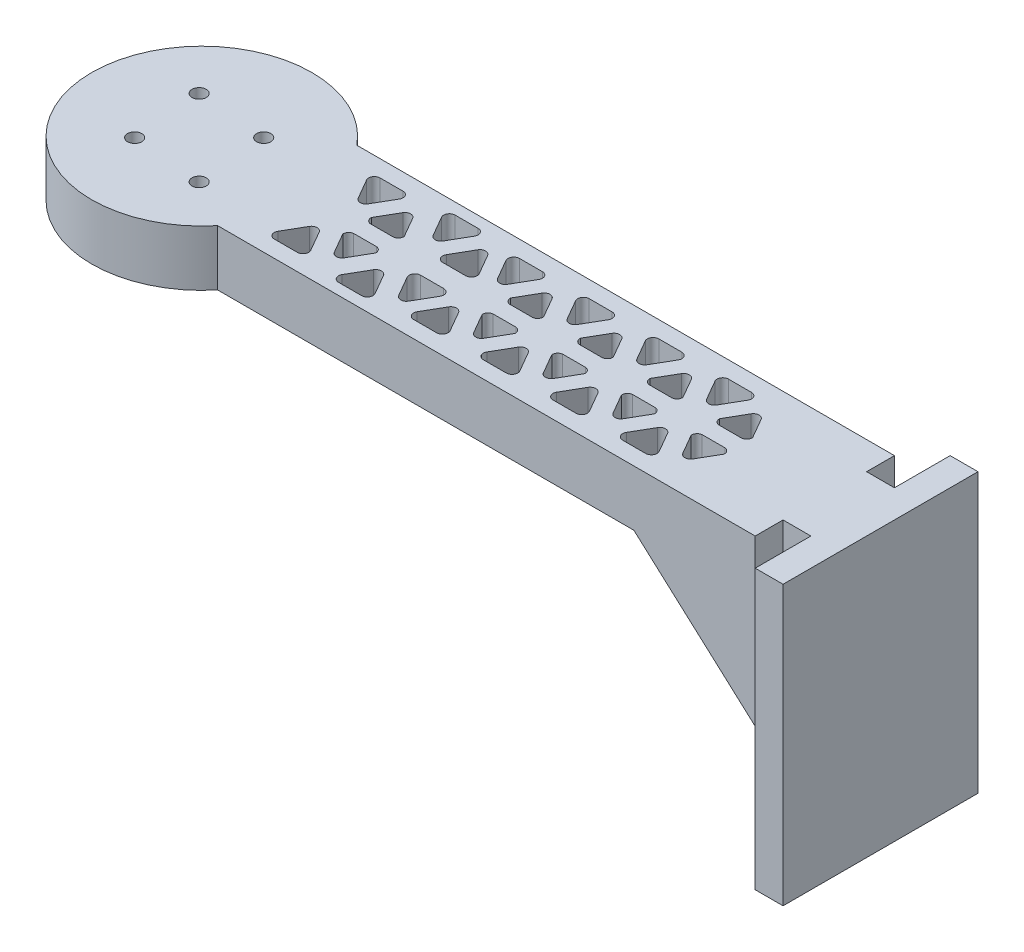
SolidWorks part; units mm, degrees
note: The reader was unsure of these and kept them because the rebuilt part matched: shared geometry of "Sketch2<3>".
ref_plane "Front Plane" through (0, 0, 0) normal (0, 0, 1) x (1, 0, 0)
ref_plane "Top Plane" through (0, 0, 0) normal (0, 1, 0) x (1, 0, 0)
ref_plane "Right Plane" through (0, 0, 0) normal (1, 0, 0) x (0, 0, -1)
sketch "Sketch1" plane through (0, 0, 0) normal (0, 1, 0) x (1, 0, 0)
  line L0 (19.7818, 0.4757) -> (121.8484, 0.4757) construction
  line L1 (15.332, 12.9757) -> (121.8484, 12.9757)
  line L2 (15.332, -12.0243) -> (121.8484, -12.0243)
  line L3 (121.8484, 12.9757) -> (121.8484, -12.0243)
  line L4 (22.5013, 9.9757) -> (26.6358, 9.9757)
  line L5 (27.5225, 8.4396) -> (25.4552, 4.8613)
  line L6 (23.682, 4.8613) -> (21.6147, 8.4396)
  line L7 (29.935, 6.6184) -> (27.8677, 3.0401)
  line L8 (33.7755, 3.0322) -> (31.7082, 6.6184)
  line L9 (28.7543, 1.9757) -> (32.8889, 1.9757)
  line L21 (37.9612, 5.8205) -> (40.0285, 9.3988)
  line L22 (34.1207, 9.3988) -> (36.188, 5.8205)
  line L23 (39.1419, 10.935) -> (35.0073, 10.935)
  line L26 (45.3949, 2.4553) -> (41.2604, 2.4553)
  line L27 (40.3737, 3.9915) -> (42.441, 7.5777)
  line L28 (44.2142, 7.5777) -> (46.2815, 3.9993)
  line L29 (35.0113, 9.9757) -> (39.1458, 9.9757) [skipped]
  line L30 (40.0325, 8.4396) -> (37.9652, 4.8613) [skipped]
  line L31 (36.192, 4.8613) -> (34.1247, 8.4396) [skipped]
  line L32 (42.445, 6.6184) -> (40.3777, 3.0401) [skipped]
  line L33 (46.2855, 3.0322) -> (44.2182, 6.6184) [skipped]
  line L34 (41.2643, 1.9757) -> (45.3989, 1.9757) [skipped]
  line L35 (47.5213, 9.9757) -> (51.6558, 9.9757)
  line L36 (52.5425, 8.4396) -> (50.4752, 4.8613)
  line L37 (48.702, 4.8613) -> (46.6347, 8.4396)
  line L38 (54.955, 6.6184) -> (52.8877, 3.0401)
  line L39 (58.7955, 3.0322) -> (56.7282, 6.6184)
  line L40 (53.7743, 1.9757) -> (57.9089, 1.9757)
  line L41 (60.0313, 9.9757) -> (64.1658, 9.9757)
  line L42 (65.0525, 8.4396) -> (62.9852, 4.8613)
  line L43 (61.212, 4.8613) -> (59.1447, 8.4396)
  line L44 (67.465, 6.6184) -> (65.3977, 3.0401)
  line L45 (71.3055, 3.0322) -> (69.2382, 6.6184)
  line L46 (66.2843, 1.9757) -> (70.4189, 1.9757)
  line L47 (72.5413, 9.9757) -> (76.6758, 9.9757)
  line L48 (77.5625, 8.4396) -> (75.4952, 4.8613)
  line L49 (73.722, 4.8613) -> (71.6547, 8.4396)
  line L50 (79.975, 6.6184) -> (77.9077, 3.0401)
  line L51 (83.8155, 3.0322) -> (81.7482, 6.6184)
  line L52 (78.7943, 1.9757) -> (82.9289, 1.9757)
  line L53 (85.0513, 9.9757) -> (89.1858, 9.9757)
  line L54 (90.0725, 8.4396) -> (88.0052, 4.8613)
  line L55 (86.232, 4.8613) -> (84.1647, 8.4396)
  line L56 (92.485, 6.6184) -> (90.4177, 3.0401)
  line L57 (96.3255, 3.0322) -> (94.2582, 6.6184)
  line L58 (91.3043, 1.9757) -> (95.4389, 1.9757)
  line L59 (91.3043, -1.0243) -> (95.4389, -1.0243)
  line L60 (96.3255, -2.0808) -> (94.2582, -5.667)
  line L61 (92.485, -5.667) -> (90.4177, -2.0887)
  line L62 (86.232, -3.9098) -> (84.1647, -7.4881)
  line L63 (90.0725, -7.4881) -> (88.0052, -3.9098)
  line L64 (85.0513, -9.0243) -> (89.1858, -9.0243)
  line L65 (78.7943, -1.0243) -> (82.9289, -1.0243)
  line L66 (83.8155, -2.0808) -> (81.7482, -5.667)
  line L67 (79.975, -5.667) -> (77.9077, -2.0887)
  line L68 (73.722, -3.9098) -> (71.6547, -7.4881)
  line L69 (77.5625, -7.4881) -> (75.4952, -3.9098)
  line L70 (72.5413, -9.0243) -> (76.6758, -9.0243)
  line L71 (66.2843, -1.0243) -> (70.4189, -1.0243)
  line L72 (71.3055, -2.0808) -> (69.2382, -5.667)
  line L73 (67.465, -5.667) -> (65.3977, -2.0887)
  line L74 (61.212, -3.9098) -> (59.1447, -7.4881)
  line L75 (65.0525, -7.4881) -> (62.9852, -3.9098)
  line L76 (60.0313, -9.0243) -> (64.1658, -9.0243)
  line L77 (53.7743, -1.0243) -> (57.9089, -1.0243)
  line L78 (58.7955, -2.0808) -> (56.7282, -5.667)
  line L79 (54.955, -5.667) -> (52.8877, -2.0887)
  line L80 (48.702, -3.9098) -> (46.6347, -7.4881)
  line L81 (52.5425, -7.4881) -> (50.4752, -3.9098)
  line L82 (47.5213, -9.0243) -> (51.6558, -9.0243)
  line L83 (44.2142, -6.6262) -> (46.2815, -3.0479)
  line L84 (40.3737, -3.0401) -> (42.441, -6.6262)
  line L85 (45.3949, -1.5039) -> (41.2604, -1.5039)
  line L86 (39.1419, -9.9836) -> (35.0073, -9.9836)
  line L87 (34.1207, -8.4474) -> (36.188, -4.8691)
  line L88 (37.9612, -4.8691) -> (40.0285, -8.4474)
  line L89 (28.7543, -1.0243) -> (32.8889, -1.0243)
  line L90 (33.7755, -2.0808) -> (31.7082, -5.667)
  line L91 (29.935, -5.667) -> (27.8677, -2.0887)
  line L92 (23.682, -3.9098) -> (21.6147, -7.4881)
  line L93 (27.5225, -7.4881) -> (25.4552, -3.9098)
  line L94 (22.5013, -9.0243) -> (26.6358, -9.0243)
  circle A0 centre (0, 0.4757) radius 19.7818
  circle A1 centre (-6.8783, 6.8783) radius 1.2799
  circle A2 centre (5.7923, 5.7923) radius 1.2799
  circle A3 centre (-5.7923, -5.7923) radius 1.2799
  circle A4 centre (6.8783, -6.8783) radius 1.2799
  arc A5 (25.4552, 4.8613) -> (23.682, 4.8613) centre (24.5686, 5.3735) cw
  arc A6 (22.5013, 9.9757) -> (21.6147, 8.4396) centre (22.5013, 8.9518) ccw
  arc A7 (26.6358, 9.9757) -> (27.5225, 8.4396) centre (26.6358, 8.9518) cw
  arc A8 (32.8889, 1.9757) -> (33.7755, 3.0322) centre (32.7524, 2.9905) ccw
  arc A9 (31.7082, 6.6184) -> (29.935, 6.6184) centre (30.8216, 6.1062) ccw
  arc A10 (28.7543, 1.9757) -> (27.8677, 3.0401) centre (28.8905, 2.9906) cw
  arc A20 (35.0073, 10.935) -> (34.1207, 9.3988) centre (35.0073, 9.911) ccw
  arc A21 (39.1419, 10.935) -> (40.0285, 9.3988) centre (39.1419, 9.911) cw
  arc A22 (36.188, 5.8205) -> (37.9612, 5.8205) centre (37.0746, 6.3327) ccw
  arc A23 (45.3949, 2.4553) -> (46.2815, 3.9993) centre (45.3995, 3.4793) ccw
  arc A24 (42.441, 7.5777) -> (44.2142, 7.5777) centre (43.3276, 7.0654) cw
  arc A25 (41.2604, 2.4553) -> (40.3737, 3.9915) centre (41.2604, 3.4793) cw
  arc A26 (37.9652, 4.8613) -> (36.192, 4.8613) centre (37.0786, 5.3735) cw [skipped]
  arc A27 (35.0113, 9.9757) -> (34.1247, 8.4396) centre (35.0113, 8.9518) ccw [skipped]
  arc A28 (39.1458, 9.9757) -> (40.0325, 8.4396) centre (39.1458, 8.9518) cw [skipped]
  arc A29 (45.3989, 1.9757) -> (46.2855, 3.0322) centre (45.2624, 2.9905) ccw [skipped]
  arc A30 (44.2182, 6.6184) -> (42.445, 6.6184) centre (43.3316, 6.1062) ccw [skipped]
  arc A31 (41.2643, 1.9757) -> (40.3777, 3.0401) centre (41.4005, 2.9906) cw [skipped]
  arc A32 (50.4752, 4.8613) -> (48.702, 4.8613) centre (49.5886, 5.3735) cw
  arc A33 (47.5213, 9.9757) -> (46.6347, 8.4396) centre (47.5213, 8.9518) ccw
  arc A34 (51.6558, 9.9757) -> (52.5425, 8.4396) centre (51.6558, 8.9518) cw
  arc A35 (57.9089, 1.9757) -> (58.7955, 3.0322) centre (57.7724, 2.9905) ccw
  arc A36 (56.7282, 6.6184) -> (54.955, 6.6184) centre (55.8416, 6.1062) ccw
  arc A37 (53.7743, 1.9757) -> (52.8877, 3.0401) centre (53.9105, 2.9906) cw
  arc A38 (62.9852, 4.8613) -> (61.212, 4.8613) centre (62.0986, 5.3735) cw
  arc A39 (60.0313, 9.9757) -> (59.1447, 8.4396) centre (60.0313, 8.9518) ccw
  arc A40 (64.1658, 9.9757) -> (65.0525, 8.4396) centre (64.1658, 8.9518) cw
  arc A41 (70.4189, 1.9757) -> (71.3055, 3.0322) centre (70.2824, 2.9905) ccw
  arc A42 (69.2382, 6.6184) -> (67.465, 6.6184) centre (68.3516, 6.1062) ccw
  arc A43 (66.2843, 1.9757) -> (65.3977, 3.0401) centre (66.4205, 2.9906) cw
  arc A44 (75.4952, 4.8613) -> (73.722, 4.8613) centre (74.6086, 5.3735) cw
  arc A45 (72.5413, 9.9757) -> (71.6547, 8.4396) centre (72.5413, 8.9518) ccw
  arc A46 (76.6758, 9.9757) -> (77.5625, 8.4396) centre (76.6758, 8.9518) cw
  arc A47 (82.9289, 1.9757) -> (83.8155, 3.0322) centre (82.7924, 2.9905) ccw
  arc A48 (81.7482, 6.6184) -> (79.975, 6.6184) centre (80.8616, 6.1062) ccw
  arc A49 (78.7943, 1.9757) -> (77.9077, 3.0401) centre (78.9305, 2.9906) cw
  arc A50 (88.0052, 4.8613) -> (86.232, 4.8613) centre (87.1186, 5.3735) cw
  arc A51 (85.0513, 9.9757) -> (84.1647, 8.4396) centre (85.0513, 8.9518) ccw
  arc A52 (89.1858, 9.9757) -> (90.0725, 8.4396) centre (89.1858, 8.9518) cw
  arc A53 (95.4389, 1.9757) -> (96.3255, 3.0322) centre (95.3024, 2.9905) ccw
  arc A54 (94.2582, 6.6184) -> (92.485, 6.6184) centre (93.3716, 6.1062) ccw
  arc A55 (91.3043, 1.9757) -> (90.4177, 3.0401) centre (91.4405, 2.9906) cw
  arc A56 (91.3043, -1.0243) -> (90.4177, -2.0887) centre (91.4405, -2.0391) ccw
  arc A57 (94.2582, -5.667) -> (92.485, -5.667) centre (93.3716, -5.1547) cw
  arc A58 (95.4389, -1.0243) -> (96.3255, -2.0808) centre (95.3024, -2.0391) cw
  arc A59 (89.1858, -9.0243) -> (90.0725, -7.4881) centre (89.1858, -8.0004) ccw
  arc A60 (85.0513, -9.0243) -> (84.1647, -7.4881) centre (85.0513, -8.0004) cw
  arc A61 (88.0052, -3.9098) -> (86.232, -3.9098) centre (87.1186, -4.422) ccw
  arc A62 (78.7943, -1.0243) -> (77.9077, -2.0887) centre (78.9305, -2.0391) ccw
  arc A63 (81.7482, -5.667) -> (79.975, -5.667) centre (80.8616, -5.1547) cw
  arc A64 (82.9289, -1.0243) -> (83.8155, -2.0808) centre (82.7924, -2.0391) cw
  arc A65 (76.6758, -9.0243) -> (77.5625, -7.4881) centre (76.6758, -8.0004) ccw
  arc A66 (72.5413, -9.0243) -> (71.6547, -7.4881) centre (72.5413, -8.0004) cw
  arc A67 (75.4952, -3.9098) -> (73.722, -3.9098) centre (74.6086, -4.422) ccw
  arc A68 (66.2843, -1.0243) -> (65.3977, -2.0887) centre (66.4205, -2.0391) ccw
  arc A69 (69.2382, -5.667) -> (67.465, -5.667) centre (68.3516, -5.1547) cw
  arc A70 (70.4189, -1.0243) -> (71.3055, -2.0808) centre (70.2824, -2.0391) cw
  arc A71 (64.1658, -9.0243) -> (65.0525, -7.4881) centre (64.1658, -8.0004) ccw
  arc A72 (60.0313, -9.0243) -> (59.1447, -7.4881) centre (60.0313, -8.0004) cw
  arc A73 (62.9852, -3.9098) -> (61.212, -3.9098) centre (62.0986, -4.422) ccw
  arc A74 (53.7743, -1.0243) -> (52.8877, -2.0887) centre (53.9105, -2.0391) ccw
  arc A75 (56.7282, -5.667) -> (54.955, -5.667) centre (55.8416, -5.1547) cw
  arc A76 (57.9089, -1.0243) -> (58.7955, -2.0808) centre (57.7724, -2.0391) cw
  arc A77 (51.6558, -9.0243) -> (52.5425, -7.4881) centre (51.6558, -8.0004) ccw
  arc A78 (47.5213, -9.0243) -> (46.6347, -7.4881) centre (47.5213, -8.0004) cw
  arc A79 (50.4752, -3.9098) -> (48.702, -3.9098) centre (49.5886, -4.422) ccw
  arc A80 (41.2604, -1.5039) -> (40.3737, -3.0401) centre (41.2604, -2.5279) ccw
  arc A81 (42.441, -6.6262) -> (44.2142, -6.6262) centre (43.3276, -6.114) ccw
  arc A82 (45.3949, -1.5039) -> (46.2815, -3.0479) centre (45.3995, -2.5278) cw
  arc A83 (36.188, -4.8691) -> (37.9612, -4.8691) centre (37.0746, -5.3813) cw
  arc A84 (39.1419, -9.9836) -> (40.0285, -8.4474) centre (39.1419, -8.9596) ccw
  arc A85 (35.0073, -9.9836) -> (34.1207, -8.4474) centre (35.0073, -8.9596) cw
  arc A86 (28.7543, -1.0243) -> (27.8677, -2.0887) centre (28.8905, -2.0391) ccw
  arc A87 (31.7082, -5.667) -> (29.935, -5.667) centre (30.8216, -5.1547) cw
  arc A88 (32.8889, -1.0243) -> (33.7755, -2.0808) centre (32.7524, -2.0391) cw
  arc A89 (26.6358, -9.0243) -> (27.5225, -7.4881) centre (26.6358, -8.0004) ccw
  arc A90 (22.5013, -9.0243) -> (21.6147, -7.4881) centre (22.5013, -8.0004) cw
  arc A91 (25.4552, -3.9098) -> (23.682, -3.9098) centre (24.5686, -4.422) ccw
  point P55 (30.8216, 6.1062)
  point P68 (37.0746, 6.3327)
  point P76 (43.3276, 7.0654)
  point P93 (43.3316, 6.1062)
  point P112 (55.8416, 6.1062)
  point P131 (68.3516, 6.1062)
  point P150 (80.8616, 6.1062)
  point P169 (93.3716, 6.1062)
  point P258 (93.3716, -5.1547)
  point P259 (80.8616, -5.1547)
  point P260 (68.3516, -5.1547)
  point P261 (55.8416, -5.1547)
  point P262 (43.3276, -6.114)
  point P263 (37.0746, -5.3813)
  point P264 (30.8216, -5.1547)
  dimension "D1" = 3
  dimension "D2" = 3
  dimension "D3" = 25
  dimension "D5" = 3
  dimension "D4" = 6
extrude "Boss-Extrude2" add sketch "Sketch1" along normal blind 10 contours A0 A4 A3 A2 A1 | L0 A0 L2 L3 A91 L93 A89 L94 A90 L92 A79 L81 A77 L82 A78 L80 A73 L75 A71 L76 A72 L74 A67 L69 A65 L70 A66 L68 A61 L63 A59 L64 A60 L62 L59 A58 L60 A57 L61 A56 L65 A64 L66 A63 | A0 L0 L3 L1 L58 A55 L56 A54 L57 A53 L53 A52 L54 A50 L55 A51 L52 A49 L50 A48 L51 A47 L47 A46 L48 A44 L49 A45 L46 A43 L44 A42 L45 A41 L41 A40 L42 A38 L43 A39 L40 A37 L38 A36
sketch "Sketch2" plane through (0, 10, 0) normal (0, 1, 0) x (1, 0, 0)
  line L0 (121.8484, 12.9757) -> (121.8484, 17.9757)
  line L2 (121.8484, 17.9757) -> (116.8484, 17.9757)
  line L3 (116.8484, 17.9757) -> (116.8484, 12.9757)
  line L4 (15.332, 12.9757) -> (121.8484, 12.9757) construction
  line L6 (121.8484, 0.4757) -> (109.1771, 0.4757) construction
  line L7 (121.8484, 12.9757) -> (121.8484, -12.0243) construction
  line L9 (116.8484, -17.0243) -> (116.8484, -12.0243)
  line L10 (121.8484, -17.0243) -> (116.8484, -17.0243)
  line L11 (121.8484, -12.0243) -> (121.8484, -17.0243)
  line L12 (116.8484, 12.9757) -> (116.8484, -12.0243)
  line L13 (121.8484, 12.9757) -> (121.8484, -12.0243)
  line L14 (116.8484, 12.9757) -> (111.8484, 12.9757)
  line L15 (111.8484, 12.9757) -> (111.8484, 7.9757)
  line L16 (111.8484, 7.9757) -> (116.8484, 7.9757)
  line L17 (116.8484, -12.0243) -> (111.8484, -12.0243)
  line L18 (111.8484, -7.0243) -> (116.8484, -7.0243)
  line L19 (111.8484, -12.0243) -> (111.8484, -7.0243)
  line L20 (116.8484, 12.9757) -> (116.8484, 7.9757)
  line L21 (116.8484, -7.0243) -> (116.8484, -12.0243)
  dimension "D1" = 5
  dimension "D2" = 5
  dimension "D3" = 5
  dimension "D4" = 5
extrude "Boss-Extrude3" add sketch "Sketch2" against normal blind 50 contours L2 L3 L12 L9 L10 L11 L13 L0
sketch "Sketch3" plane through (0, 0, 12.0243) normal (0, 0, 1) x (1, 0, 0)
  line L0 (90.0725, 0) -> (116.8484, -24.0811)
  line L1 (116.8484, -40) -> (116.8484, 10) construction
  line L2 (90.0725, 0) -> (116.8484, 0)
  line L3 (15.332, 0) -> (116.8484, 0) construction
  line L4 (116.8484, 0) -> (116.8484, -24.0811)
extrude "Boss-Extrude4" add sketch "Sketch3" against normal up to surface (25 mm away) contours L0 L4 L2 up to face at (66.0902, 5, -12.9757)
extrude "Cut-Extrude1" cut sketch "Sketch2<3>" against normal up to vertex contours L15 L16 L12 L14 | L19 L17 L12 L18
sketch "Sketch2<3>" plane through (0, 10, 0) normal (0, 1, 0) x (1, 0, 0) same geometry as "Sketch2"
